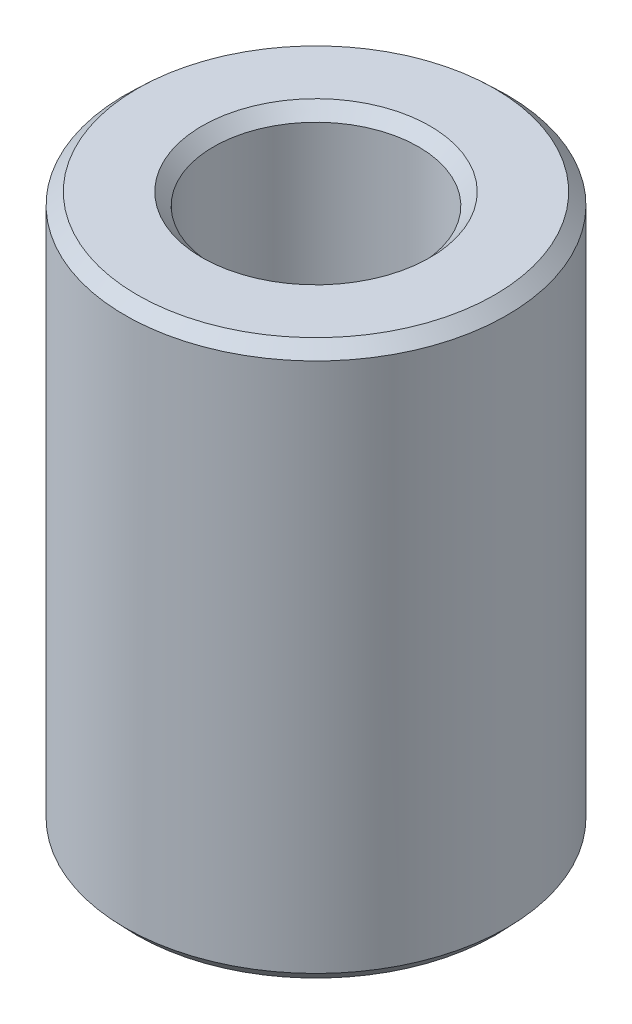
SolidWorks part; units mm, degrees
ref_plane "Front Plane" through (0, 0, 0) normal (0, 0, 1) x (1, 0, 0)
ref_plane "Top Plane" through (0, 0, 0) normal (0, 1, 0) x (1, 0, 0)
ref_plane "Right Plane" through (0, 0, 0) normal (1, 0, 0) x (0, 0, -1)
sketch "Sketch1" plane through (0, 0, 0) normal (0, 1, 0) x (1, 0, 0)
  circle A0 centre (0, 0) radius 55
  dimension "SLEEVE_OD" = 110
extrude "Boss-Extrude1" add sketch "Sketch1" along normal blind 159.6774
sketch "Sketch2" plane through (0, 0, 0) normal (0, 1, 0) x (1, 0, 0)
  circle A0 centre (0, 0) radius 29.5195
  dimension "BORE_D" = 59.039
extrude "Cut-Extrude1" cut sketch "Sketch2" along normal through all
chamfer "Chamfer1" distance 3.333 angle 46.528 4 edges at (0, 159.6774, 29.5195) (0, 0, 29.5195) (0, 0, 55) (0, 159.6774, 55) first distance on face at (0, 159.6774, 29.5195) first distance on face at (0, 0, 29.5195) first distance on face at (0, 159.6774, 55)
